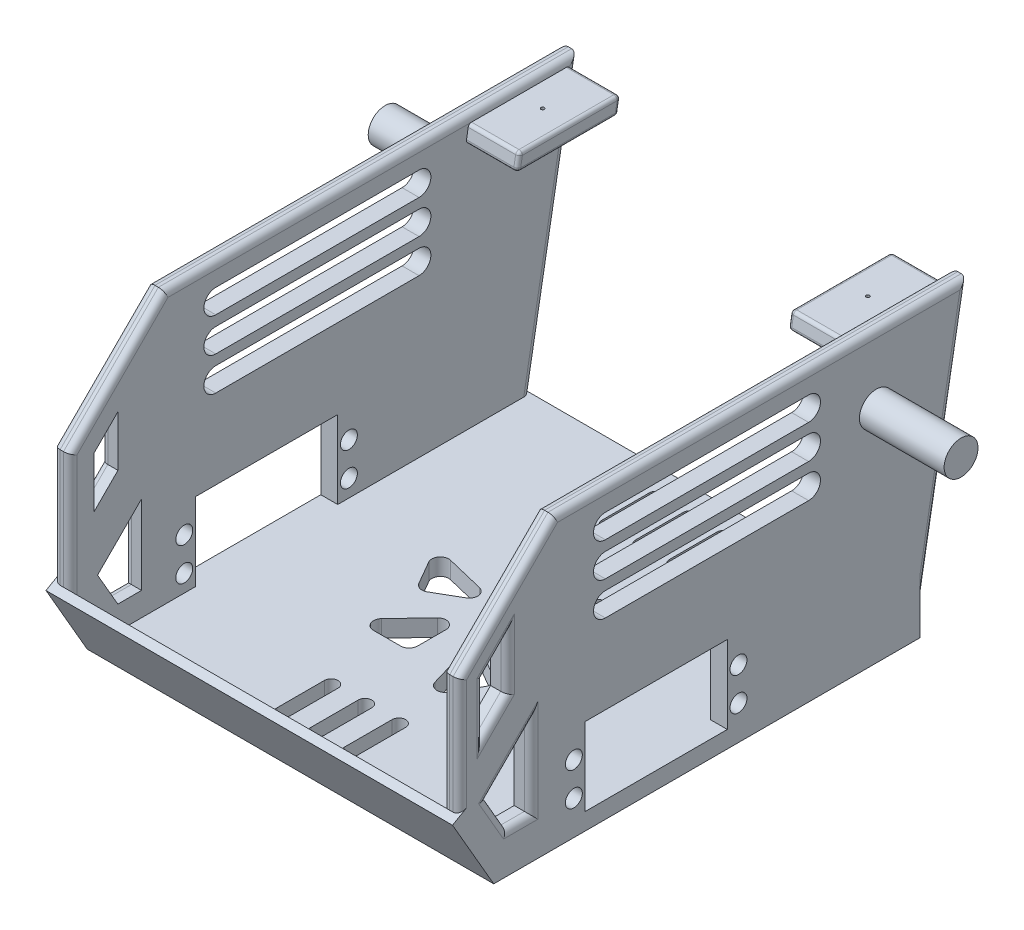
SolidWorks part; units mm, degrees
ref_plane "Front Plane" through (0, 0, 0) normal (0, 0, 1) x (1, 0, 0)
ref_plane "Top Plane" through (0, 0, 0) normal (0, 1, 0) x (1, 0, 0)
ref_plane "Right Plane" through (0, 0, 0) normal (1, 0, 0) x (0, 0, -1)
sketch "Sketch1" plane through (0, 0, 0) normal (1, 0, 0) x (0, 0, -1)
  line L0 (121.1207, 0) -> (-121.1207, 0) construction
  line L1 (0, 97.2701) -> (0, -97.2701) construction
  line L2 (-72.9469, 52) -> (-44.9469, 80)
  line L3 (-44.9469, 80) -> (77.0531, 80)
  line L4 (77.0531, 80) -> (62.9469, 0)
  line L5 (62.9469, 0) -> (-62.9469, 0)
  line L6 (-62.9469, 0) -> (-72.9469, 17.3205)
  line L7 (-72.9469, 17.3205) -> (-72.9469, 52)
  line L8 (30, 70) -> (-30, 70) construction
  line L9 (30, 66.5) -> (-30, 66.5)
  line L10 (30, 73.5) -> (-30, 73.5)
  line L11 (30, 60) -> (-30, 60) construction
  line L12 (30, 56.5) -> (-30, 56.5)
  line L13 (30, 63.5) -> (-30, 63.5)
  line L14 (30, 50) -> (-30, 50) construction
  line L15 (30, 46.5) -> (-30, 46.5)
  line L16 (30, 53.5) -> (-30, 53.5)
  line L17 (-58.8759, 56.1716) -> (-65.9469, 49.1005)
  line L18 (-65.9469, 49.1005) -> (-65.9469, 34.1005)
  line L19 (-65.9469, 34.1005) -> (-58.8759, 41.1716)
  line L20 (-58.8759, 41.1716) -> (-58.8759, 56.1716)
  line L21 (-64.9055, 17.3923) -> (-58.9055, 7)
  line L22 (-58.9055, 7) -> (-51.9055, 7)
  line L23 (-51.9055, 7) -> (-51.9055, 30.3923)
  line L24 (-51.9055, 30.3923) -> (-64.9055, 17.3923)
  arc A0 (30, 66.5) -> (30, 73.5) centre (30, 70) ccw
  arc A1 (-30, 73.5) -> (-30, 66.5) centre (-30, 70) ccw
  arc A2 (30, 56.5) -> (30, 63.5) centre (30, 60) ccw
  arc A3 (-30, 63.5) -> (-30, 56.5) centre (-30, 60) ccw
  arc A4 (30, 46.5) -> (30, 53.5) centre (30, 50) ccw
  arc A5 (-30, 53.5) -> (-30, 46.5) centre (-30, 50) ccw
  point P4 (0, 0)
  point P8 (0, 0)
  point P15 (0, 0)
  point P16 (0, 70)
  point P22 (0, 60)
  point P29 (0, 50)
  dimension "D11" = 3.5
  dimension "D1" = 150
  dimension "D2" = 120
  dimension "D3" = 20
  dimension "D4" = 80
  dimension "D5" = 135
  dimension "D6" = 122
  dimension "D7" = 100
  dimension "D8" = 10
  dimension "D9" = 10
  dimension "D10" = 10
  dimension "D12" = 30
  dimension "D13" = 7
  dimension "D14" = 7
  dimension "D15" = 15
  dimension "D16" = 10
  dimension "D17" = 7
  dimension "D18" = 7
  dimension "D19" = 12
  dimension "D20" = 7
sketch "Sketch6" plane through (0, 0, 0) normal (0, 1, 0) x (1, 0, 0)
  line L0 (0, -62.9469) -> (0, 62.9469) construction
  line L1 (-60, -62.9469) -> (60, -62.9469)
  line L2 (-60, -62.9469) -> (-60, 62.9469)
  line L3 (-60, 62.9469) -> (60, 62.9469)
  line L4 (60, -62.9469) -> (60, 62.9469)
  line L5 (-60, -62.9469) -> (60, 62.9469) construction
  line L6 (-60, 62.9469) -> (60, -62.9469) construction
  line L7 (7.0318, 18.3929) -> (7.0318, 10)
  line L10 (9.5318, 20.8929) -> (17.5318, 20.8929)
  line L15 (19.3415, 16.668) -> (11.3415, 8.2751)
  line L16 (22.8597, 2.1916) -> (26.8597, -4.7366)
  line L17 (19.4447, 3.1067) -> (12.1762, -1.0898)
  line L18 (24.1057, -8.4162) -> (12.8372, -5.6844)
  line L19 (13.3279, -18.7013) -> (9.3279, -25.6295)
  line L20 (12.4128, -15.2862) -> (5.1443, -11.0898)
  line L21 (4.7642, -25.0842) -> (1.4957, -13.9595)
  line L22 (-9.5318, -20.8929) -> (-17.5318, -20.8929)
  line L23 (-7.0318, -18.3929) -> (-7.0318, -10)
  line L24 (-19.3415, -16.668) -> (-11.3415, -8.2751)
  line L25 (-22.8597, -2.1916) -> (-26.8597, 4.7366)
  line L26 (-19.4447, -3.1067) -> (-12.1762, 1.0898)
  line L27 (-24.1057, 8.4162) -> (-12.8372, 5.6844)
  line L28 (-13.3279, 18.7013) -> (-9.3279, 25.6295)
  line L29 (-12.4128, 15.2862) -> (-5.1443, 11.0898)
  line L30 (-4.7642, 25.0842) -> (-1.4957, 13.9595)
  line L31 (0, 40.9469) -> (0, 54.9469) construction
  line L32 (-2, 40.9469) -> (-2, 54.9469)
  line L33 (2, 40.9469) -> (2, 54.9469)
  line L34 (12, 40.9469) -> (12, 54.9469)
  line L35 (8, 40.9469) -> (8, 54.9469)
  line L36 (10, 40.9469) -> (10, 54.9469) construction
  line L37 (-10, 40.9469) -> (-10, 54.9469) construction
  line L38 (-12, 40.9469) -> (-12, 54.9469)
  line L39 (-8, 40.9469) -> (-8, 54.9469)
  line L40 (0, 0) -> (-125.7444, 0) construction
  line L41 (0, -40.9469) -> (0, -54.9469) construction
  line L42 (-2, -40.9469) -> (-2, -54.9469)
  line L43 (2, -40.9469) -> (2, -54.9469)
  line L44 (10, -40.9469) -> (10, -54.9469) construction
  line L45 (8, -40.9469) -> (8, -54.9469)
  line L46 (12, -40.9469) -> (12, -54.9469)
  line L47 (-10, -40.9469) -> (-10, -54.9469) construction
  line L48 (-12, -40.9469) -> (-12, -54.9469)
  line L49 (-8, -40.9469) -> (-8, -54.9469)
  arc A6 (9.5318, 20.8929) -> (7.0318, 18.3929) centre (9.5318, 18.3929) ccw
  arc A7 (19.3415, 16.668) -> (17.5318, 20.8929) centre (17.5318, 18.3929) ccw
  arc A8 (7.0318, 10) -> (11.3415, 8.2751) centre (9.5318, 10) ccw
  arc A9 (12.1762, -1.0898) -> (12.8372, -5.6844) centre (13.4262, -3.2548) ccw
  arc A10 (24.1057, -8.4162) -> (26.8597, -4.7366) centre (24.6947, -5.9866) ccw
  arc A11 (22.8597, 2.1916) -> (19.4447, 3.1067) centre (20.6947, 0.9416) ccw
  arc A12 (5.1443, -11.0898) -> (1.4957, -13.9595) centre (3.8943, -13.2548) ccw
  arc A13 (4.7642, -25.0842) -> (9.3279, -25.6295) centre (7.1628, -24.3795) ccw
  arc A14 (13.3279, -18.7013) -> (12.4128, -15.2862) centre (11.1628, -17.4513) ccw
  arc A15 (-7.0318, -10) -> (-11.3415, -8.2751) centre (-9.5318, -10) ccw
  arc A16 (-19.3415, -16.668) -> (-17.5318, -20.8929) centre (-17.5318, -18.3929) ccw
  arc A17 (-9.5318, -20.8929) -> (-7.0318, -18.3929) centre (-9.5318, -18.3929) ccw
  arc A18 (-12.1762, 1.0898) -> (-12.8372, 5.6844) centre (-13.4262, 3.2548) ccw
  arc A19 (-24.1057, 8.4162) -> (-26.8597, 4.7366) centre (-24.6947, 5.9866) ccw
  arc A20 (-22.8597, -2.1916) -> (-19.4447, -3.1067) centre (-20.6947, -0.9416) ccw
  arc A21 (-5.1443, 11.0898) -> (-1.4957, 13.9595) centre (-3.8943, 13.2548) ccw
  arc A22 (-4.7642, 25.0842) -> (-9.3279, 25.6295) centre (-7.1628, 24.3795) ccw
  arc A23 (-13.3279, 18.7013) -> (-12.4128, 15.2862) centre (-11.1628, 17.4513) ccw
  arc A24 (-2, 40.9469) -> (2, 40.9469) centre (0, 40.9469) ccw
  arc A25 (2, 54.9469) -> (-2, 54.9469) centre (0, 54.9469) ccw
  arc A26 (8, 40.9469) -> (12, 40.9469) centre (10, 40.9469) ccw
  arc A27 (12, 54.9469) -> (8, 54.9469) centre (10, 54.9469) ccw
  arc A28 (-12, 40.9469) -> (-8, 40.9469) centre (-10, 40.9469) ccw
  arc A29 (-8, 54.9469) -> (-12, 54.9469) centre (-10, 54.9469) ccw
  arc A30 (-2, -40.9469) -> (2, -40.9469) centre (0, -40.9469) cw
  arc A31 (2, -54.9469) -> (-2, -54.9469) centre (0, -54.9469) cw
  arc A32 (8, -40.9469) -> (12, -40.9469) centre (10, -40.9469) cw
  arc A33 (12, -54.9469) -> (8, -54.9469) centre (10, -54.9469) cw
  arc A34 (-12, -40.9469) -> (-8, -40.9469) centre (-10, -40.9469) cw
  arc A35 (-8, -54.9469) -> (-12, -54.9469) centre (-10, -54.9469) cw
  point P0 (0, 0)
  point P10 (0, 0)
  point P17 (0, 47.9469)
  point P67 (0, 0)
  point P76 (10, 47.9469)
  point P82 (-10, 47.9469)
  point P90 (0, -47.9469)
  point P97 (10, -47.9469)
  point P104 (-10, -47.9469)
  dimension "D1" = 5
  dimension "80" = 120
  dimension "D2" = 10
  dimension "D5" = 15
  dimension "D6" = 7
  dimension "D3" = 8
  dimension "D7" = 2
  dimension "D8" = 2
  dimension "D9" = 2
  dimension "D4" = 6
extrude "Boss-Extrude1" add sketch "Sketch6" against normal blind 5
extrude "Boss-Extrude2" add sketch "Sketch1" against normal blind 5 from surface starting at face at (60, -2.5, 0)
extrude "Boss-Extrude3" add sketch "Sketch1<2>" along normal blind 5 from surface starting at face at (-60, -2.5, 0)
sketch "Sketch1<2>" plane through (0, 0, 0) normal (1, 0, 0) x (0, 0, -1) same geometry as "Sketch1"
sketch "Sketch9" plane through (0, -27.2568, 47.2102) normal (0, -0.5, 0.866) x (1, 0, 0)
  line L1 (-60, 51.4735) -> (60, 51.4735)
  line L2 (-60, 51.4735) -> (-60, 27.1433)
  line L3 (-60, 27.1433) -> (60, 27.1433)
  line L4 (60, 51.4735) -> (60, 27.1433)
extrude "Boss-Extrude5" add sketch "Sketch9" along normal up to vertex (2.5 mm away) up to point (-60, -5, 62.9469)
sketch "Sketch10" plane through (-60, 0, 0) normal (-1, 0, 0) x (0, 0, 1)
  line L0 (-62.9469, 0) -> (62.9469, 0) construction
  line L1 (-62.9469, 0) -> (62.9469, 0)
  line L2 (0, 0) -> (0, 80) construction
  line L3 (44.9469, 80) -> (-77.0531, 80) construction
  line L4 (15, 20) -> (15, 0) construction
  line L5 (-6, 0) -> (36, 0)
  line L6 (-6, 0) -> (-6, 20)
  line L7 (-6, 20) -> (36, 20)
  line L8 (36, 0) -> (36, 20)
  line L9 (39.3, 10) -> (-9.3, 10) construction
  line L10 (-9.3, 5.1) -> (-9.3, 14.9) construction
  line L12 (-6, 20) -> (36, 20)
  line L13 (-6, 20) -> (-6, 23)
  line L14 (-6, 23) -> (36, 23)
  line L15 (36, 20) -> (36, 23)
  circle A0 centre (-9.3, 14.9) radius 2.5
  circle A1 centre (-9.3, 5.1) radius 2.5
  circle A2 centre (39.3, 5.1) radius 2.5
  circle A3 centre (39.3, 14.9) radius 2.5
  point P16 (15, 10)
  point P20 (-9.3, 10)
  dimension "D6" = 5
  dimension "D1" = 20
  dimension "D2" = 42
  dimension "D3" = 15
  dimension "D4" = 48.6
  dimension "D5" = 9.8
  dimension "D7" = 3
extrude "Cut-Extrude1" cut sketch "Sketch10" against normal up to surface (120 mm away) contours A0 | A1 | L1 L8 L7 L6 | L7 L15 L14 L13 | A3 | A2 region at (-60, 10, 15) region at (-60, 21.5, 15) region at (-60, 14.9, -9.3) region at (-60, 5.1, -9.3) region at (-60, 5.1, 39.3) region at (-60, 14.9, 39.3) up to face at (60, 29.4239, 15.7441)
fillet "Fillet1" radius 2 32 edges at (-55, 66, 58.9469) (-60, 66, 58.9469) (-55, 34.6603, 72.9469) (-60, 34.6603, 72.9469) (-60, 80, -16.0531) (-55, 80, -16.0531) (-60, 40, -70) (-55, 40, -70) (55, 40, -70) (60, 40, -70) (60, 34.6603, 72.9469) (55, 34.6603, 72.9469) (60, 66, 58.9469) (55, 66, 58.9469) (55, 80, -16.0531) (60, 80, -16.0531) (-60, 7, 55.4055) (-60, 12.1962, 61.9055) (-60, 23.8923, 58.4055) (-60, 18.6962, 51.9055) (-60, 37.636, 62.4114) (-60, 41.6005, 65.9469) (-60, 52.636, 62.4114) (-60, 48.6716, 58.8759) (60, 12.1962, 61.9055) (60, 7, 55.4055) (60, 18.6962, 51.9055) (60, 23.8923, 58.4055) (60, 41.6005, 65.9469) (60, 37.636, 62.4114) (60, 48.6716, 58.8759) (60, 52.636, 62.4114)
sketch "Sketch11" plane through (60, 0, 0) normal (1, 0, 0) x (0, 0, -1)
  line L0 (0, 0) -> (50, 0) construction
  line L1 (50, 0) -> (50, 60) construction
  circle A0 centre (50, 60) radius 5
  dimension "D1" = 10
  dimension "D2" = 60
  dimension "0" = 50
extrude "Boss-Extrude6" add sketch "Sketch11" along normal blind 25 contours A0 region at (60, 60, -50)
extrude "Boss-Extrude7" add sketch "Sketch11<3>" against normal blind 25 from surface starting at face at (-60, 15.7355, 56.819)
sketch "Sketch11<3>" plane through (60, 0, 0) normal (1, 0, 0) x (0, 0, -1) same geometry as "Sketch11"
sketch "Sketch12" plane through (-55, 0, 0) normal (1, 0, 0) x (0, 0, -1)
  line L0 (74.6696, 78) -> (44.6696, 78)
  line L1 (74.6696, 78) -> (-44.1185, 78) construction
  line L2 (44.6696, 78) -> (43.8013, 73.076)
  line L3 (43.8013, 73.076) -> (73.8013, 73.076)
  line L4 (62.9469, 11.5175) -> (74.6696, 78) construction
  line L5 (74.6696, 78) -> (73.8013, 73.076)
  dimension "D1" = 30
  dimension "D2" = 5
extrude "Boss-Extrude8" add sketch "Sketch12" along normal blind 15
extrude "Boss-Extrude9" add sketch "Sketch12<2>" against normal blind 15 from surface starting at face at (55, 5.1, 41.8)
sketch "Sketch12<2>" plane through (-55, 0, 0) normal (1, 0, 0) x (0, 0, -1) same geometry as "Sketch12"
fillet "Fillet3" radius 1 8 edges at (47.5, 73.076, -43.8013) (40, 75.538, -44.2355) (40, 73.076, -58.8013) (40, 75.538, -74.2355) (47.5, 73.076, -73.8013) (47.5, 78, -44.6696) (40, 78, -59.6696) (47.5, 78, -74.6696)
fillet "Fillet4" radius 1 8 edges at (-47.5, 73.076, -43.8013) (-40, 75.538, -44.2355) (-40, 73.076, -58.8013) (-40, 75.538, -74.2355) (-47.5, 73.076, -73.8013) (-47.5, 78, -44.6696) (-40, 78, -59.6696) (-47.5, 78, -74.6696)
sketch "Sketch13" plane through (0, 78, 0) normal (0, 1, 0) x (1, 0, 0)
  line L0 (-48, 73.4778) -> (-48, 45.5087) construction
  line L1 (-41, 73.4778) -> (-55, 73.4778) construction
  line L2 (-55, 45.5087) -> (-41, 45.5087) construction
  line L3 (48, 73.4778) -> (48, 45.5087) construction
  line L4 (55, 73.4778) -> (41, 73.4778) construction
  line L5 (41, 45.5087) -> (55, 45.5087) construction
  circle A0 centre (-48, 59.4932) radius 0.5
  circle A1 centre (48, 59.4932) radius 0.5
  dimension "D1" = 1
  dimension "D2" = 1
extrude "Cut-Extrude2" cut sketch "Sketch13" against normal blind 10
